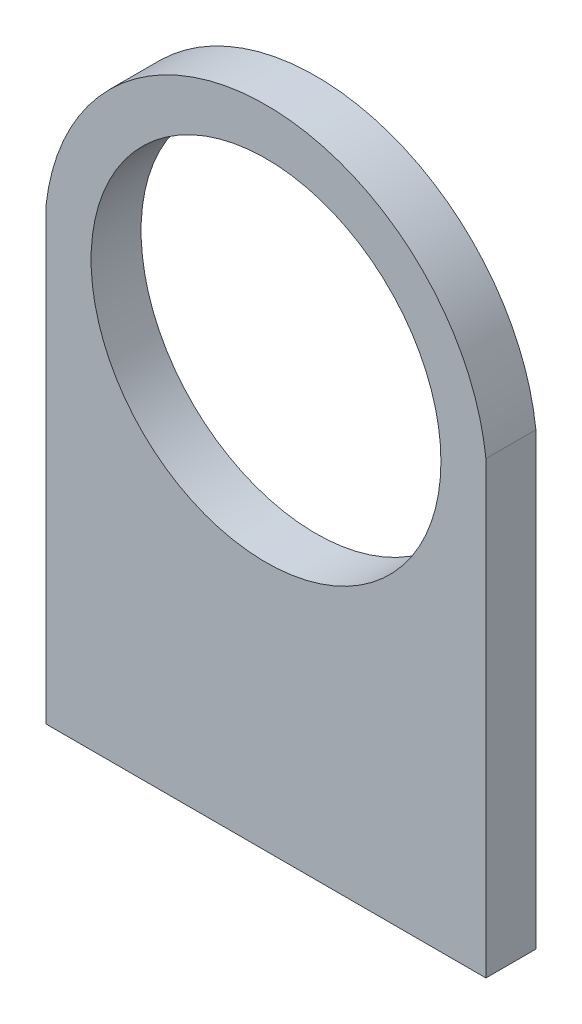
SolidWorks part; units mm, degrees
ref_plane "Plan de face" through (0, 0, 0) normal (0, 0, 1) x (1, 0, 0)
ref_plane "Plan de dessus" through (0, 0, 0) normal (0, 1, 0) x (1, 0, 0)
ref_plane "Plan de droite" through (0, 0, 0) normal (1, 0, 0) x (0, 0, -1)
sketch "Esquisse1" plane through (0, 0, 0) normal (0, 0, 1) x (1, 0, 0)
  line L0 (0, 0) -> (0, -45)
  line L1 (0, -45) -> (44, -45)
  line L2 (44, -45) -> (44, 0)
  arc A0 (0, 0) -> (44, 0) centre (22, -2.5) cw
  circle A1 centre (22, -2.5) radius 17.5
  dimension "D4" = 35
  dimension "D1" = 45
  dimension "D2" = 44
  dimension "D3" = 2.5
extrude "Boss.-Extru.1" add sketch "Esquisse1" along normal blind 5
